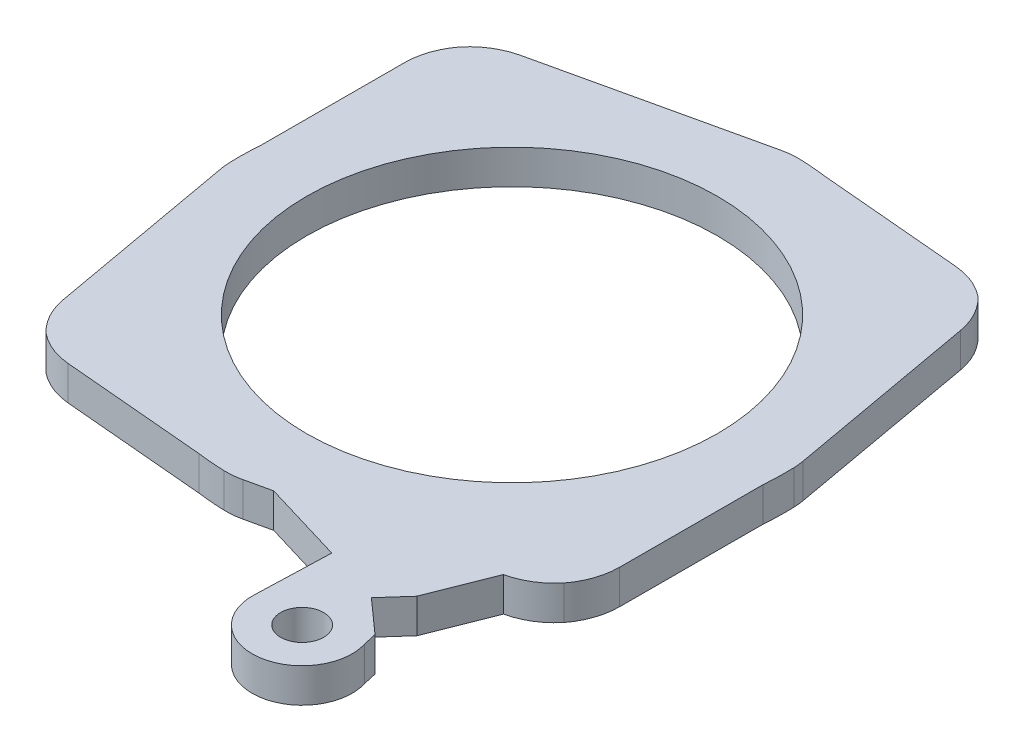
SolidWorks part; units mm, degrees
ref_plane "Front Plane" through (0, 0, 0) normal (0, 0, 1) x (1, 0, 0)
ref_plane "Top Plane" through (0, 0, 0) normal (0, 1, 0) x (1, 0, 0)
ref_plane "Right Plane" through (0, 0, 0) normal (1, 0, 0) x (0, 0, -1)
sketch "Sketch1" plane through (0, 0, 0) normal (0, 1, 0) x (1, 0, 0)
  line L0 (0, 0) -> (0, 30.6197) construction
  line L1 (-30.6197, 0) -> (30.6197, 0) construction
  line L2 (0, 0) -> (21.6514, 21.6514) construction
  line L3 (0, 0) -> (25.2584, -1.9879) construction
  line L4 (0, 0) -> (21.6514, -21.6514) construction
  line L5 (0, 25.8572) -> (-22.4927, 20.7761)
  line L6 (0, 0) -> (0, -30.6197) construction
  line L7 (0, 0) -> (-21.6514, 21.6514) construction
  line L8 (0, 0) -> (-21.6514, -21.6514) construction
  line L9 (-25.3018, -1.326) -> (-21.6514, -21.6514)
  line L10 (0, -25.8572) -> (22.4927, -20.7761)
  line L11 (25.3018, 1.326) -> (21.6514, 21.6514)
  line L13 (3.375, 25.636) -> (18.6401, 24.2922)
  line L14 (25.2584, -1.9879) -> (25.2345, -17.3432)
  line L15 (25.2345, -17.3432) -> (25.1925, -17.1621)
  line L16 (-3.375, -25.636) -> (-18.6401, -24.2922)
  line L17 (-18.6401, -24.2922) -> (-18.3762, -24.1896)
  line L18 (-25.2584, 1.9879) -> (-25.2345, 17.3432)
  circle A0 centre (0, 0) radius 25.8572 construction
  circle A1 centre (0, 0) radius 30.6197 construction
  arc A2 (0, 25.8572) -> (6.6923, 24.9761) centre (0, 0) cw construction
  arc A3 (21.6514, 21.6514) -> (15.3098, 26.5174) centre (0, 0) ccw construction
  arc A4 (25.3018, 1.326) -> (25.2584, -1.9879) centre (0, 0) cw
  arc A5 (25.2345, -17.3432) -> (22.4927, -20.7761) centre (0, 0) cw
  arc A7 (25.3018, 1.326) -> (24.7828, -5.2678) centre (0, 0) cw construction
  arc A8 (22.4927, -20.7761) -> (27.2824, -13.9011) centre (0, 0) ccw construction
  arc A9 (0, -25.8572) -> (-3.375, -25.636) centre (0, 0) cw
  circle A10 centre (0, 0) radius 19.05
  arc A11 (0, 25.8572) -> (3.375, 25.636) centre (0, 0) cw
  arc A12 (18.6401, 24.2922) -> (21.6514, 21.6514) centre (0, 0) cw
  arc A13 (-18.6401, -24.2922) -> (-21.6514, -21.6514) centre (0, 0) cw
  arc A14 (-24.2922, 18.6401) -> (-21.6514, 21.6514) centre (0, 0) cw [skipped]
  arc A15 (-25.8572, 0) -> (-25.636, 3.375) centre (0, 0) cw [skipped]
  arc A16 (-18.6401, -24.2922) -> (-21.6514, -21.6514) centre (0, 0) cw [skipped]
  arc A17 (0, -25.8572) -> (-3.375, -25.636) centre (0, 0) cw [skipped]
  arc A18 (24.2922, -18.6401) -> (21.6514, -21.6514) centre (0, 0) cw [skipped]
  arc A19 (25.8572, 0) -> (25.636, -3.375) centre (0, 0) cw [skipped]
  arc A20 (0, -25.8572) -> (-6.6923, -24.9761) centre (0, 0) cw construction
  arc A21 (-21.6514, -21.6514) -> (-15.3099, -26.5174) centre (0, 0) ccw construction
  arc A22 (-25.3018, -1.326) -> (-25.2584, 1.9879) centre (0, 0) cw
  arc A23 (-25.2345, 17.3432) -> (-22.4927, 20.7761) centre (0, 0) cw
  point P9 (3.375, 25.636)
  point P17 (18.6401, 24.2922)
  point P24 (25.2584, -1.9879)
  point P26 (24.8054, -17.0483)
  point P30 (0, 0)
  point P35 (-3.3071, -25.1197)
  point P37 (-18.3231, -23.8791)
  point P53 (0, 0)
  dimension "D1" = 6.8072
  dimension "D2" = 4.7625
  dimension "D8" = 38.1
  dimension "D9" = 2
  dimension "D3" = 45
  dimension "D4" = 45
  dimension "D5" = 15
  dimension "D6" = 15
  dimension "D10" = 25.3365
  dimension "D7" = 4
extrude "Boss-Extrude1" add sketch "Sketch1" along normal mid plane 3.175 contours A3 A2 | L18 A22 L9 A13 L16 A9 L10 A5 L14 A4 L11 A12 L13 A11 L5 A23 A10 region at (1.6438, 0, -25.0794)
fillet "Fillet1" radius 6.35 12 edges at (25.3018, 0, -1.326) (0, 0, -25.8572) (-25.3018, 0, 1.326) (-22.4927, 0, -20.7761) (-25.2345, 0, -17.3432) (-21.6514, 0, 21.6514) (-18.6401, 0, 24.2922) (0, 0, 25.8572) (18.6401, 0, -24.2922) (21.6514, 0, -21.6514) (25.2345, 0, 17.3432) (22.4927, 0, 20.7761)
sketch "Sketch3" plane through (0, 1.5875, 0) normal (0, 1, 0) x (1, 0, 0)
  line L0 (-5.2454, -74.8035) -> (17.5608, -36.6501) construction
  line L1 (0, 0) -> (17.5608, -36.6501) construction
  line L2 (13.2945, -38.6943) -> (6.4459, -24.4011)
  line L4 (0, 0) -> (-3.3071, -25.1197) construction
  line L5 (0, 0) -> (8.5697, -1.1282) construction
  line L6 (8.5697, -1.1282) -> (0.0326, -65.9737) construction
  line L7 (21.8271, -34.6059) -> (15.9128, -22.2625)
  line L8 (6.4459, -24.4011) -> (15.9128, -22.2625)
  line L9 (0.7402, -25.69) -> (20.4428, -21.2392) construction
  circle A0 centre (0.0326, -65.9737) radius 3.175 construction
  circle A2 centre (17.5608, -36.6501) radius 1.5558
  circle A4 centre (0.0326, -65.9737) radius 10.287 construction
  arc A5 (13.2945, -38.6943) -> (21.8271, -34.6059) centre (17.5608, -36.6501) ccw
  point P9 (-5.2454, -74.8035)
  dimension "D2" = 65.405
  dimension "D3" = 20.574
  dimension "D1" = 8.6436
  dimension "D5" = 3.1115
  dimension "D6" = 3.175
  dimension "D8" = 6.35
  dimension "D4" = 44.45
  dimension "D7" = 40.64
sketch "Sketch4" plane through (0, 1.5875, 0) normal (0, 1, 0) x (1, 0, 0)
  line L0 (18.1711, -26.9815) -> (20.4428, -21.2392)
  line L1 (11.9001, -23.169) -> (16.9898, -22.0192)
  line L2 (0, 0) -> (15.1564, -34.6093) construction
  line L3 (0, 0) -> (-3.3071, -25.1197) construction
  line L4 (23.927, -19.1041) -> (0, 0) construction
  line L5 (-0.8735, -25.8424) -> (0, 0) construction
  line L6 (-8.8171, -6.6276) -> (43.1894, -48.1514) construction
  line L7 (10.9524, 7.8573) -> (8.9623, -51.0179) construction
  line L8 (10.5235, -34.4527) -> (10.7597, -27.4677)
  line L9 (0.7402, -25.69) -> (20.4428, -21.2392) construction
  line L10 (19.3057, -32.0041) -> (16.179, -29.2134)
  line L11 (16.179, -29.2134) -> (18.1711, -26.9815)
  line L12 (3.0736, -25.1629) -> (10.7597, -27.4677)
  line L13 (3.0736, -25.1629) -> (11.9001, -23.169)
  line L14 (19.3057, -32.0041) -> (19.5846, -33.2385)
  line L15 (20.4428, -21.2392) -> (16.9898, -22.0192)
  circle A0 centre (0, 0) radius 37.7825 construction
  circle A1 centre (15.1564, -34.6093) radius 1.9939
  arc A3 (10.5235, -34.4527) -> (19.5846, -33.2385) centre (15.1564, -34.6093) ccw
  arc A5 (-0.8735, -25.8424) -> (0.7402, -25.69) centre (-0.659, -19.4961) ccw construction
  dimension "D1" = 75.565
  dimension "D4" = 3.9878
  dimension "D5" = 9.271
  dimension "D2" = 10.6807
  dimension "D3" = 10.6807
  dimension "D6" = 31.15
  dimension "D7" = 6.985
  dimension "D8" = 35.52
  dimension "D9" = 4.191
  dimension "D10" = 2.8301
extrude "Boss-Extrude2" add sketch "Sketch4" against normal up to surface (3.175 mm away) up to face at (0, -1.5875, 0)
